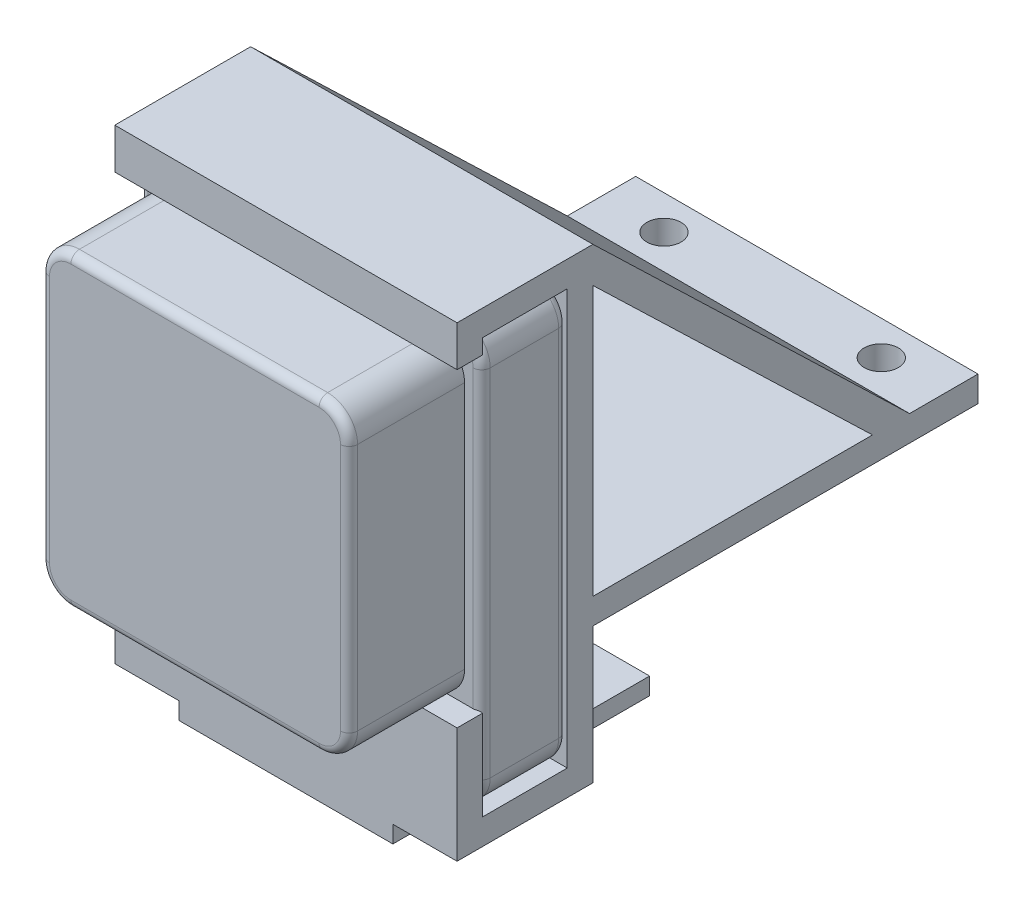
SolidWorks part; units mm, degrees
ref_plane "Front Plane" through (0, 0, 0) normal (0, 0, 1) x (1, 0, 0)
ref_plane "Top Plane" through (0, 0, 0) normal (0, 1, 0) x (1, 0, 0)
ref_plane "Right Plane" through (0, 0, 0) normal (1, 0, 0) x (0, 0, -1)
sketch "Sketch1" plane through (0, 0, 0) normal (0, 0, 1) x (1, 0, 0)
  line L0 (0, 20) -> (0, 0) construction
  line L1 (-18, 18) -> (18, 18)
  line L2 (-18, 18) -> (-18, -18)
  line L3 (-18, -18) -> (18, -18)
  line L4 (18, 18) -> (18, -18)
  line L5 (-18, 18) -> (18, -18) construction
  line L6 (-18, -18) -> (18, 18) construction
  line L7 (-20, 20) -> (20, 20)
  line L8 (-20, 20) -> (-20, -28.5)
  line L9 (-20, -28.5) -> (20, -28.5)
  line L10 (20, 20) -> (20, -28.5)
  point P0 (0, 0)
  dimension "D1" = 36
  dimension "D2" = 40
  dimension "D3" = 48.5
  dimension "D4" = 2
extrude "Boss-Extrude1" add sketch "Sketch1" along normal blind 13.5 contours L2 L3 L4 L1
extrude "Boss-Extrude2" add sketch "Sketch1<3>" against normal blind 10 separate body contours L10 L7 L8 L9 L1 L4 L3 L2 | L4 L1 L2 L3 region at (0, 0, 0) region at (0, 19.3713, 0)
sketch "Sketch1<3>" plane through (0, 0, 0) normal (0, 0, 1) x (1, 0, 0) same geometry as "Sketch1"
fillet "Fillet1" radius 3.5 4 edges at (20, 20, -5) (-20, -28.5, -5) (20, -28.5, -5) (-20, 20, -5)
fillet "Fillet2" radius 3.5 4 edges at (18, 18, 6.75) (18, -18, 6.75) (-18, -18, 6.75) (-18, 18, 6.75)
fillet "Fillet3" radius 1 8 edges at (-18.9749, 18.9749, 0) (0, 20, 0) (18.9749, 18.9749, 0) (20, -4.25, 0) (18.9749, -27.4749, 0) (0, -28.5, 0) (-18.9749, -27.4749, 0) (-20, -4.25, 0)
fillet "Fillet4" radius 1 8 edges at (-18.9749, 18.9749, -10) (-20, -4.25, -10) (-18.9749, -27.4749, -10) (0, -28.5, -10) (18.9749, -27.4749, -10) (20, -4.25, -10) (18.9749, 18.9749, -10) (0, 20, -10)
fillet "Fillet5" radius 1 8 edges at (-16.9749, 16.9749, 13.5) (0, 18, 13.5) (16.9749, 16.9749, 13.5) (18, 0, 13.5) (16.9749, -16.9749, 13.5) (0, -18, 13.5) (-16.9749, -16.9749, 13.5) (-18, 0, 13.5)
sketch "Sketch2" plane through (0, 0, 0) normal (1, 0, 0) x (0, 0, -1)
  line L0 (-2.875, -18) -> (-2.875, -31.5)
  line L1 (0, -18) -> (-12.5, -18) construction
  line L2 (-2.875, -31.5) -> (13, -31.5)
  line L3 (13, -31.5) -> (13, 20)
  line L4 (-2.875, -18) -> (0.125, -18)
  line L6 (0.125, -18) -> (0.125, -28.5)
  line L7 (0.125, -28.5) -> (10, -28.5)
  line L8 (10, -28.5) -> (10, 20)
  line L10 (9, -28.5) -> (1, -28.5) construction
  line L11 (10, 16.5) -> (10, 19) construction
  line L12 (0, -18) -> (0, -14.5) construction
  line L13 (0.125, -28.5) -> (0.125, -31.5) construction
  line L14 (10, -28.5) -> (13, -28.5) construction
  line L16 (13, 20) -> (13, 23)
  line L17 (13, 23) -> (-2.875, 23)
  line L18 (-2.875, 23) -> (-2.875, 18.25)
  line L19 (-2.875, 18.25) -> (0.125, 18.25)
  line L21 (0.125, 18.25) -> (0.125, 20)
  line L22 (0.125, 20) -> (10, 20)
  line L24 (10, 20) -> (10, 23) construction
  line L25 (1, 20) -> (9, 20) construction
  line L26 (-12.5, 18) -> (0, 18) construction
  line L27 (0.125, 20) -> (-2.875, 20) construction
  dimension "D1" = 0.125
  dimension "D2" = 3
  dimension "D3" = 0.25
extrude "Boss-Extrude3" add sketch "Sketch2" along normal up to surface and the other way up to surface separate body up to face at (20, -4.25, -5) other way up to face at (-20, -4.25, -5)
sketch "Sketch3" plane through (0, 0, 0) normal (1, 0, 0) x (0, 0, -1)
  line L1 (58, -15.625) -> (10, -15.625)
  line L2 (50, -12.625) -> (58, -12.625)
  line L3 (10, 23) -> (10, -15.625)
  line L4 (13, 18.8354) -> (13, -12.625)
  line L5 (13, -12.625) -> (45.6747, -12.625)
  line L6 (45.6747, -12.625) -> (13, 18.8354)
  line L7 (10, -28.5) -> (10, 20) construction
  line L8 (58, -12.625) -> (58, -15.625)
  line L9 (10, 23) -> (13, 23)
  line L10 (13, 23) -> (50, -12.625)
  line L11 (45.6747, -12.625) -> (50, -12.625) construction
  dimension "D1" = 15.875
  dimension "D2" = 48
  dimension "D3" = 3
  dimension "D4" = 3
  dimension "D5" = 3
  dimension "D6" = 8
extrude "Boss-Extrude4" add sketch "Sketch3" along normal up to surface and the other way up to surface up to face at (20, -2.7917, -2.9167) other way up to face at (-20, -2.7917, -2.9167)
sketch "Sketch8" plane through (0, 0, 0) normal (1, 0, 0) x (0, 0, -1)
  line L0 (-2.875, -31.5) -> (-2.875, -33.5)
  line L1 (-2.875, -33.5) -> (27.125, -33.5)
  line L2 (27.125, -33.5) -> (27.125, -31.5)
  line L3 (27.125, -31.5) -> (13, -31.5)
  line L20 (50, -12.625) -> (13, 23)
  line L21 (13, 23) -> (-2.875, 23)
  line L22 (-2.875, 23) -> (-2.875, 18.25)
  line L23 (-2.875, 18.25) -> (0.125, 18.25)
  line L24 (0.125, 18.25) -> (0.125, 20)
  line L25 (0.125, 20) -> (10, 20)
  line L26 (10, 20) -> (10, -28.5)
  line L27 (10, -28.5) -> (0.125, -28.5)
  line L28 (0.125, -28.5) -> (0.125, -18)
  line L29 (0.125, -18) -> (-2.875, -18)
  line L30 (-2.875, -18) -> (-2.875, -31.5)
  line L31 (-2.875, -31.5) -> (13, -31.5)
  line L32 (13, -31.5) -> (13, -15.625)
  line L33 (13, -15.625) -> (58, -15.625)
  line L34 (58, -15.625) -> (58, -12.625)
  line L35 (58, -12.625) -> (50, -12.625)
  line L47 (-2.875, -31.5) -> (13, -31.5)
  dimension "D1" = 30
  dimension "D2" = 0
  dimension "D3" = 2
extrude "Boss-Extrude5" add sketch "Sketch8" along normal mid plane 25
sketch "Sketch9" plane through (0, -12.625, 0) normal (0, 1, 0) x (1, 0, 0)
  line L0 (12.7, 54) -> (20, 54) construction
  line L1 (20, 50) -> (20, 58) construction
  line L2 (0, 58) -> (0, 50) construction
  line L3 (20, 58) -> (-20, 58) construction
  line L4 (20, 50) -> (-20, 50) construction
  circle A0 centre (12.7, 54) radius 2
  circle A1 centre (-12.7, 54) radius 2
  dimension "D1" = 4
  dimension "D2" = 7.3
extrude "Cut-Extrude3" cut sketch "Sketch9" against normal through all
